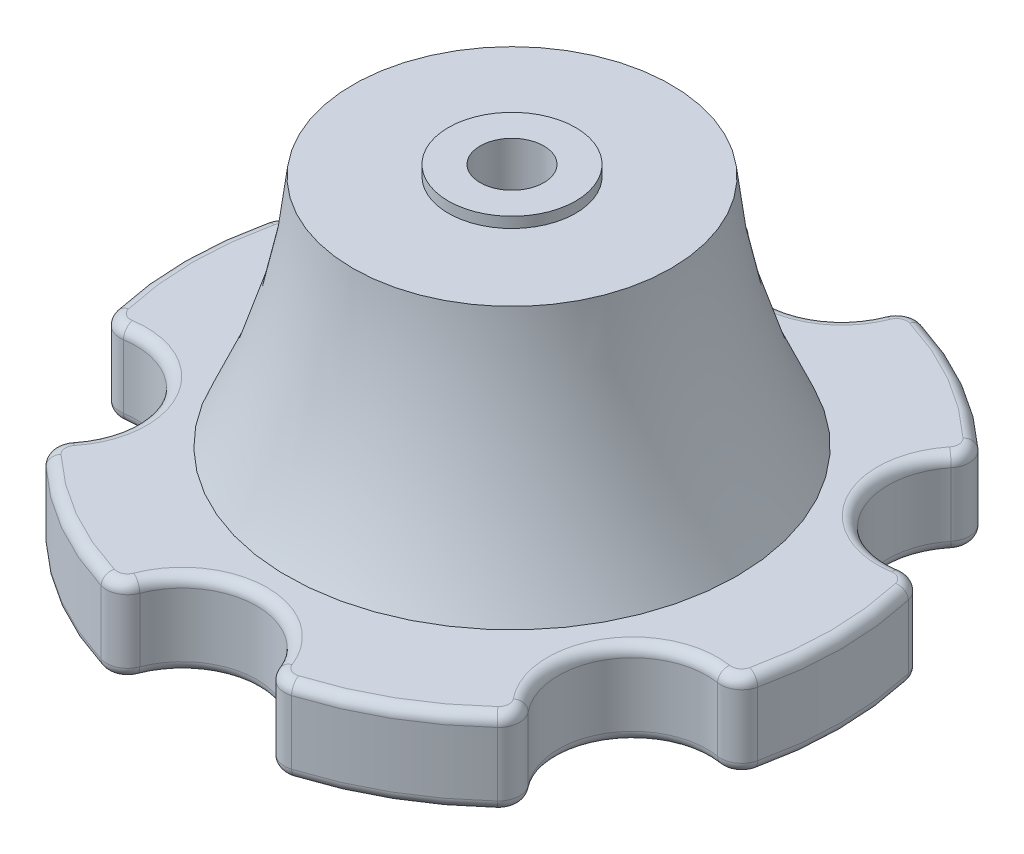
SolidWorks part; units mm, degrees
ref_plane "Спереди" through (0, 0, 0) normal (0, 0, 1) x (1, 0, 0)
ref_plane "Сверху" through (0, 0, 0) normal (0, 1, 0) x (1, 0, 0)
ref_plane "Справа" through (0, 0, 0) normal (1, 0, 0) x (0, 0, -1)
sketch "Эскиз1" plane through (0, 0, 0) normal (0, 1, 0) x (1, 0, 0)
  circle A0 centre (0, 0) radius 15.53 construction
  arc A1 (-3.4777, 15.1356) -> (3.4777, 15.1356) centre (0, 15.53) ccw
  arc A2 (3.4777, 15.1356) -> (11.369, 10.5796) centre (0, 0) cw
  arc A3 (11.369, 10.5796) -> (14.8467, 4.556) centre (13.4494, 7.765) ccw
  arc A4 (14.8467, 4.556) -> (14.8467, -4.556) centre (0, 0) cw
  arc A5 (14.8467, -4.556) -> (11.369, -10.5796) centre (13.4494, -7.765) ccw
  arc A6 (11.369, -10.5796) -> (3.4777, -15.1356) centre (0, 0) cw
  arc A7 (3.4777, -15.1356) -> (-3.4777, -15.1356) centre (0, -15.53) ccw
  arc A8 (-3.4777, -15.1356) -> (-11.369, -10.5796) centre (0, 0) cw
  arc A9 (-11.369, -10.5796) -> (-14.8467, -4.556) centre (-13.4494, -7.765) ccw
  arc A10 (-14.8467, -4.556) -> (-14.8467, 4.556) centre (0, 0) cw
  arc A11 (-14.8467, 4.556) -> (-11.369, 10.5796) centre (-13.4494, 7.765) ccw
  arc A12 (-11.369, 10.5796) -> (-3.4777, 15.1356) centre (0, 0) cw
  point P0 (-6.4579, 16.554)
  point P30 (0, 0)
  dimension "D1" = 3.5
  dimension "D3" = 6
  dimension "D2" = 15.53
extrude "Бобышка-Вытянуть1" add sketch "Эскиз1" along normal blind 15
sketch "Эскиз2" plane through (0, 0, 0) normal (0, 0, 1) x (1, 0, 0)
  line L0 (0, -1000) -> (0, 49000) construction
  line L1 (-15.6, 31) -> (-15.6, 4)
  line L2 (-15.6, 31) -> (-10.6, 31)
  line L3 (-15.6, 4) -> (-10.6, 4)
  line L4 (-3.4777, 0) -> (3.4777, 0) construction
  arc A0 (-10.6, 31) -> (-10.6, 4) centre (-37.3909, 17.5) cw
  dimension "D4" = 30
  dimension "D1" = 15.6
  dimension "D2" = 27
  dimension "D3" = 5
  dimension "D5" = 4
revolve "Вырез-Повернуть1" cut sketch "Эскиз2" angle 360 about L0
sketch "Эскиз3" plane through (0, 0, 0) normal (0, -1, 0) x (1, 0, 0)
  circle A0 centre (0, 0) radius 1.5
  dimension "D1" = 3
extrude "Вырез-Вытянуть1" cut sketch "Эскиз3" against normal blind 15
sketch "Эскиз4" plane through (0, 0, 0) normal (0, -1, 0) x (1, 0, 0)
  line L1 (1.5877, 2.75) -> (-1.5877, 2.75)
  line L2 (-1.5877, 2.75) -> (-3.1754, 0)
  line L3 (-3.1754, 0) -> (-1.5877, -2.75)
  line L4 (-1.5877, -2.75) -> (1.5877, -2.75)
  line L5 (1.5877, -2.75) -> (3.1754, 0)
  line L6 (3.1754, 0) -> (1.5877, 2.75)
  circle A1 centre (0, 0) radius 2.75 construction
  dimension "D1" = 5.5
extrude "Вырез-Вытянуть2" cut sketch "Эскиз4" against normal blind 4
fillet "Скругление1" radius 1 12 edges at (-3.4777, 2, -15.1356) (-11.369, 2, -10.5796) (3.4777, 2, -15.1356) (11.369, 2, -10.5796) (14.8467, 2, -4.556) (14.8467, 2, 4.556) (11.369, 2, 10.5796) (3.4777, 2, 15.1356) (-3.4777, 2, 15.1356) (-14.8467, 2, -4.556) (-11.369, 2, 10.5796) (-14.8467, 2, 4.556)
fillet "Скругление2" radius 0.5 48 edges at (10.4183, 4, 6.015) (10.9451, 4, 10.6598) (7.765, 4, 13.4494) (3.7592, 4, 14.8086) (0, 4, 12.03) (-3.7592, 4, 14.8086) (-7.765, 4, 13.4494) (-10.9451, 4, 10.6598) (-10.4183, 4, 6.015) (-14.7042, 4, 4.1488) (-15.53, 4, 0) (-14.7042, 4, -4.1488) (-10.4183, 4, -6.015) (-10.9451, 4, -10.6598) (-7.765, 4, -13.4494) (-3.7592, 4, -14.8086) (0, 4, -12.03) (3.7592, 4, -14.8086) (7.765, 4, -13.4494) (10.9451, 4, -10.6598) (10.4183, 4, -6.015) (14.7042, 4, -4.1488) (15.53, 4, 0) (-14.7042, 0, -4.1488) (-10.4183, 0, -6.015) (-10.9451, 0, -10.6598) (-7.765, 0, -13.4494) (-3.7592, 0, -14.8086) (0, 0, -12.03) (3.7592, 0, -14.8086) (7.765, 0, -13.4494) (10.9451, 0, -10.6598) (10.4183, 0, -6.015) (14.7042, 0, -4.1488) (15.53, 0, 0) (14.7042, 0, 4.1488) (10.4183, 0, 6.015) (10.9451, 0, 10.6598) (7.765, 0, 13.4494) (3.7592, 0, 14.8086) (0, 0, 12.03) (-3.7592, 0, 14.8086) (-7.765, 0, 13.4494) (-10.9451, 0, 10.6598) (-10.4183, 0, 6.015) (-14.7042, 0, 4.1488) (14.7042, 4, 4.1488) (-15.53, 0, 0)
sketch "Эскиз5" plane through (0, 15, 0) normal (0, 1, 0) x (1, 0, 0)
  circle A0 centre (0, 0) radius 3
  circle A1 centre (0, 0) radius 1.5
  circle A2 centre (0, 0) radius 1.5 construction
  dimension "D1" = 6
extrude "Бобышка-Вытянуть2" add sketch "Эскиз5" along normal blind 0.5
